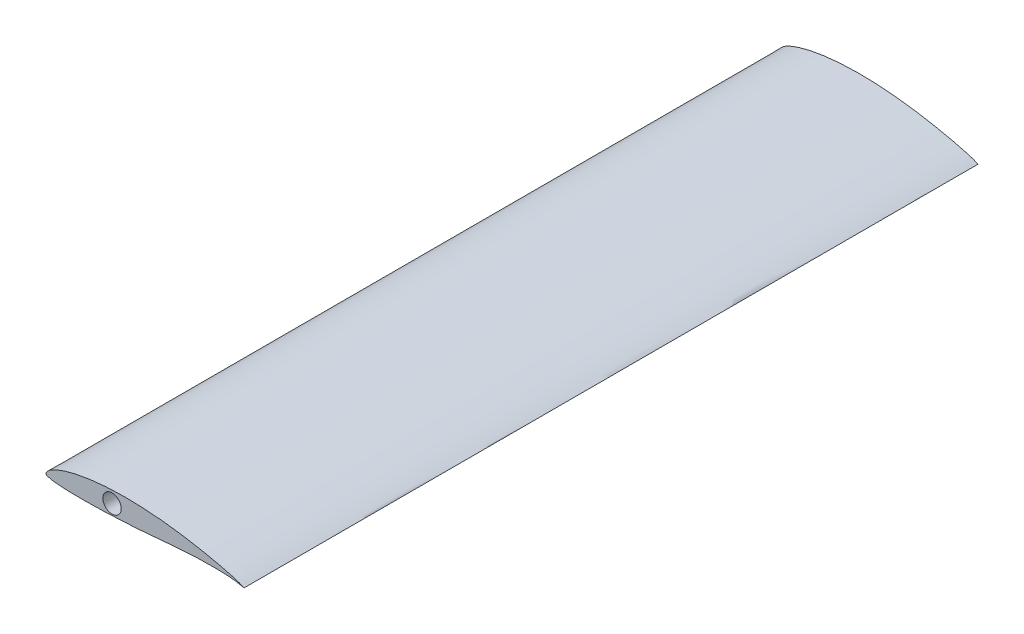
SolidWorks part; units mm, degrees
ref_plane "Front Plane" through (0, 0, 0) normal (0, 0, 1) x (1, 0, 0)
ref_plane "Top Plane" through (0, 0, 0) normal (0, 1, 0) x (1, 0, 0)
ref_plane "Right Plane" through (0, 0, 0) normal (1, 0, 0) x (0, 0, -1)
curve "Curve1"
  spline degree 3 poles (267.933, 0.5337, 0) (270.49, -0.1564, 0) (268.2375, 0.6665, 0) (266.5672, 1.4668, 0) (262.6756, 3.0154, 0) (257.9132, 4.5724, 0) (251.732, 6.3325, 0) (244.4112, 8.2376, 0) (235.9576, 10.2728, 0) (226.5142, 12.3893, 0) (216.1934, 14.5409, 0) (205.1313, 16.6775, 0) (193.4567, 18.7298, 0) (181.2977, 20.6324, 0) (168.7678, 22.3117, 0) (155.9753, 23.7079, 0) (143.0353, 24.8049, 0) (130.0617, 25.5802, 0) (117.1734, 26.0003, 0) (104.4837, 26.0576, 0) (92.1044, 25.7531, 0) (80.1395, 25.0742, 0) (68.69, 24.0381, 0) (57.8509, 22.6699, 0) (47.7143, 21.0125, 0) (38.3732, 19.0872, 0) (29.9084, 16.9558, 0) (22.399, 14.6444, 0) (15.9079, 12.2159, 0) (10.4843, 9.7202, 0) (6.177, 7.2209, 0) (2.9612, 4.7412, 0) (0.9766, 2.4261, 0) (0.0237, 0.7907, 0) (-0.0162, -0.4697, 0) (0.8003, -1.8361, 0) (3.4921, -2.6295, 0) (7.308, -3.6627, 0) (12.6566, -4.3991, 0) (19.3194, -5.0329, 0) (27.2905, -5.4698, 0) (36.4622, -5.7387, 0) (46.7414, -5.84, 0) (58.0105, -5.7702, 0) (70.1434, -5.5368, 0) (83.0071, -5.1408, 0) (96.4629, -4.5659, 0) (110.374, -3.827, 0) (124.6167, -2.893, 0) (139.0995, -1.7363, 0) (153.7348, -0.4008, 0) (168.4097, 0.8923, 0) (182.9339, 2.0414, 0) (197.0782, 2.9592, 0) (210.6044, 3.579, 0) (223.2667, 3.8744, 0) (234.8405, 3.8186, 0) (245.0477, 3.4533, 0) (253.7786, 2.7629, 0) (260.4407, 1.9422, 0) (265.7815, 0.9299, 0) (267.933, 0.5337, 0) (270.49, -0.1564, 0) (268.2375, 0.6665, 0) knots -0.016249 -0.007187 -0.001789 0 0.001694 0.006395 0.013462 0.022754 0.034367 0.048191 0.064031 0.081681 0.100894 0.121432 0.143025 0.165434 0.188439 0.211855 0.235496 0.259144 0.282615 0.305702 0.328232 0.35003 0.370944 0.390817 0.409506 0.426857 0.442733 0.457018 0.469615 0.48045 0.489472 0.49673 0.502329 0.506256 0.506442 0.509182 0.513914 0.521178 0.530944 0.543145 0.55767 0.574384 0.59311 0.613638 0.635744 0.659184 0.683714 0.709076 0.735036 0.76143 0.788184 0.815057 0.841645 0.867514 0.892232 0.915364 0.936485 0.9552 0.971104 0.983751 0.992813 0.998211 1 1.001694 1.006395 1.013462 periodic
sketch "Sketch1" plane through (0, 0, 0) normal (0, 0, 1) x (1, 0, 0)
  line L0 (270, 0) -> (0, 0) construction
  line L1 (0, -23.2448) -> (0, 51.8173) construction
  line L2 (90, 9.6033) -> (90, 0) construction
  line L3 (0, 26.0183) -> (162.1091, 26.0183) construction
  line L4 (0, -5.812) -> (132.6055, -5.812) construction
  circle A0 centre (90, 9.6033) radius 12.5
  spline S0 degree 3 poles (267.933, 0.5337) (270.49, -0.1564) (268.2375, 0.6665) (266.5672, 1.4668) (262.6756, 3.0154) (257.9132, 4.5724) (251.732, 6.3325) (244.4112, 8.2376) (235.9576, 10.2728) (226.5142, 12.3893) (216.1934, 14.5409) (205.1313, 16.6775) (193.4567, 18.7298) (181.2977, 20.6324) (168.7678, 22.3117) (155.9753, 23.7079) (143.0353, 24.8049) (130.0617, 25.5802) (117.1734, 26.0003) (104.4837, 26.0576) (92.1044, 25.7531) (80.1395, 25.0742) (68.69, 24.0381) (57.8509, 22.6699) (47.7143, 21.0125) (38.3732, 19.0872) (29.9084, 16.9558) (22.399, 14.6444) (15.9079, 12.2159) (10.4843, 9.7202) (6.177, 7.2209) (2.9612, 4.7412) (0.9766, 2.4261) (0.0237, 0.7907) (-0.0162, -0.4697) (0.8003, -1.8361) (3.4921, -2.6295) (7.308, -3.6627) (12.6566, -4.3991) (19.3194, -5.0329) (27.2905, -5.4698) (36.4622, -5.7387) (46.7414, -5.84) (58.0105, -5.7702) (70.1434, -5.5368) (83.0071, -5.1408) (96.4629, -4.5659) (110.374, -3.827) (124.6167, -2.893) (139.0995, -1.7363) (153.7348, -0.4008) (168.4097, 0.8923) (182.9339, 2.0414) (197.0782, 2.9592) (210.6044, 3.579) (223.2667, 3.8744) (234.8405, 3.8186) (245.0477, 3.4533) (253.7786, 2.7629) (260.4407, 1.9422) (265.7815, 0.9299) (267.933, 0.5337) (270.49, -0.1564) (268.2375, 0.6665) knots -0.016249 -0.007187 -0.001789 0 0.001694 0.006395 0.013462 0.022754 0.034367 0.048191 0.064031 0.081681 0.100894 0.121432 0.143025 0.165434 0.188439 0.211855 0.235496 0.259144 0.282615 0.305702 0.328232 0.35003 0.370944 0.390817 0.409506 0.426857 0.442733 0.457018 0.469615 0.48045 0.489472 0.49673 0.502329 0.506256 0.506442 0.509182 0.513914 0.521178 0.530944 0.543145 0.55767 0.574384 0.59311 0.613638 0.635744 0.659184 0.683714 0.709076 0.735036 0.76143 0.788184 0.815057 0.841645 0.867514 0.892232 0.915364 0.936485 0.9552 0.971104 0.983751 0.992813 0.998211 1 1.001694 1.006395 1.013462 only from (270, 0) to (270, 0) construction
  spline S1 degree 3 poles (267.933, 0.5337) (270.49, -0.1564) (268.2375, 0.6665) (266.5672, 1.4668) (262.6756, 3.0154) (257.9132, 4.5724) (251.732, 6.3325) (244.4112, 8.2376) (235.9576, 10.2728) (226.5142, 12.3893) (216.1934, 14.5409) (205.1313, 16.6775) (193.4567, 18.7298) (181.2977, 20.6324) (168.7678, 22.3117) (155.9753, 23.7079) (143.0353, 24.8049) (130.0617, 25.5802) (117.1734, 26.0003) (104.4837, 26.0576) (92.1044, 25.7531) (80.1395, 25.0742) (68.69, 24.0381) (57.8509, 22.6699) (47.7143, 21.0125) (38.3732, 19.0872) (29.9084, 16.9558) (22.399, 14.6444) (15.9079, 12.2159) (10.4843, 9.7202) (6.177, 7.2209) (2.9612, 4.7412) (0.9766, 2.4261) (0.0237, 0.7907) (-0.0162, -0.4697) (0.8003, -1.8361) (3.4921, -2.6295) (7.308, -3.6627) (12.6566, -4.3991) (19.3194, -5.0329) (27.2905, -5.4698) (36.4622, -5.7387) (46.7414, -5.84) (58.0105, -5.7702) (70.1434, -5.5368) (83.0071, -5.1408) (96.4629, -4.5659) (110.374, -3.827) (124.6167, -2.893) (139.0995, -1.7363) (153.7348, -0.4008) (168.4097, 0.8923) (182.9339, 2.0414) (197.0782, 2.9592) (210.6044, 3.579) (223.2667, 3.8744) (234.8405, 3.8186) (245.0477, 3.4533) (253.7786, 2.7629) (260.4407, 1.9422) (265.7815, 0.9299) (267.933, 0.5337) (270.49, -0.1564) (268.2375, 0.6665) knots -0.016249 -0.007187 -0.001789 0 0.001694 0.006395 0.013462 0.022754 0.034367 0.048191 0.064031 0.081681 0.100894 0.121432 0.143025 0.165434 0.188439 0.211855 0.235496 0.259144 0.282615 0.305702 0.328232 0.35003 0.370944 0.390817 0.409506 0.426857 0.442733 0.457018 0.469615 0.48045 0.489472 0.49673 0.502329 0.506256 0.506442 0.509182 0.513914 0.521178 0.530944 0.543145 0.55767 0.574384 0.59311 0.613638 0.635744 0.659184 0.683714 0.709076 0.735036 0.76143 0.788184 0.815057 0.841645 0.867514 0.892232 0.915364 0.936485 0.9552 0.971104 0.983751 0.992813 0.998211 1 1.001694 1.006395 1.013462 only from (270, 0) to (270, 0)
  point P12 (162.1091, 26.0183)
  dimension "D1" = 25
  dimension "D2" = 90
  dimension "D3" = 31.8303
  dimension "D4" = 16.415
extrude "Boss-Extrude1" add sketch "Sketch1" along normal blind 1000 contours S1
extrude "Cut-Extrude1" cut sketch "Sketch1<3>" along normal through all contours A0
sketch "Sketch1<3>" plane through (0, 0, 0) normal (0, 0, 1) x (1, 0, 0) same geometry as "Sketch1"
